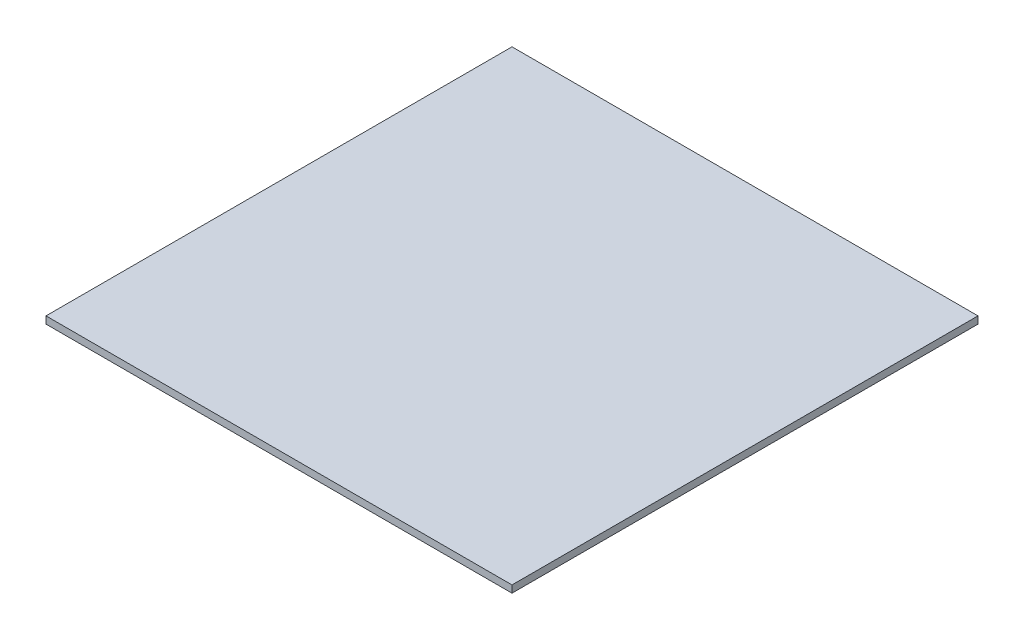
SolidWorks part; units mm, degrees
ref_plane "Front Plane" through (0, 0, 0) normal (0, 0, 1) x (1, 0, 0)
ref_plane "Top Plane" through (0, 0, 0) normal (0, 1, 0) x (1, 0, 0)
ref_plane "Right Plane" through (0, 0, 0) normal (1, 0, 0) x (0, 0, -1)
sketch "Sketch1" plane through (0, 0, 0) normal (0, 1, 0) x (1, 0, 0)
  line L1 (-325, -325) -> (325, -325)
  line L2 (-325, -325) -> (-325, 325)
  line L3 (-325, 325) -> (325, 325)
  line L4 (325, -325) -> (325, 325)
  line L5 (-325, -325) -> (325, 325) construction
  line L6 (-325, 325) -> (325, -325) construction
  point P0 (0, 0)
  dimension "D1" = 650
  dimension "D2" = 650
extrude "Boss-Extrude1" add sketch "Sketch1" against normal blind 10
